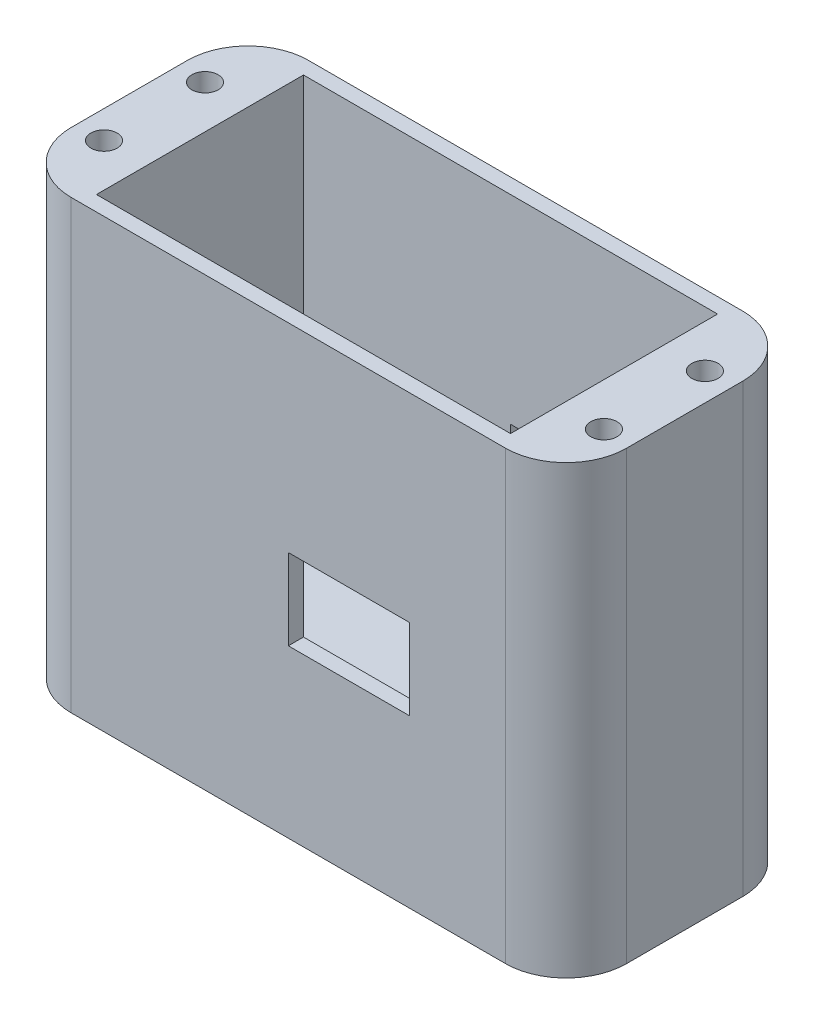
SolidWorks part; units mm, degrees
ref_plane "Front Plane" through (0, 0, 0) normal (0, 0, 1) x (1, 0, 0)
ref_plane "Top Plane" through (0, 0, 0) normal (0, 1, 0) x (1, 0, 0)
ref_plane "Right Plane" through (0, 0, 0) normal (1, 0, 0) x (0, 0, -1)
sketch "Sketch1" plane through (0, 0, 0) normal (0, 1, 0) x (1, 0, 0)
  line L1 (-27.5, 11) -> (27.5, 11)
  line L2 (-27.5, 11) -> (-27.5, -11)
  line L3 (-27.5, -11) -> (27.5, -11)
  line L4 (27.5, 11) -> (27.5, -11)
  line L5 (-27.5, 11) -> (27.5, -11) construction
  line L6 (-27.5, -11) -> (27.5, 11) construction
  point P4 (0, 0)
  dimension "D1" = 22
  dimension "D2" = 55
extrude "Boss-Extrude1" add sketch "Sketch1" along normal blind 2
sketch "Sketch2" plane through (0, 2, 0) normal (0, 1, 0) x (1, 0, 0)
  line L0 (-27.5, -11) -> (-27.5, 11)
  line L1 (-27.5, 11) -> (27.5, 11)
  line L2 (27.5, 11) -> (27.5, -11)
  line L3 (27.5, -11) -> (20.5, -11)
  line L4 (-27.5, -11) -> (27.5, -11) construction
  line L5 (20.5, -11) -> (20.5, 9.5)
  line L6 (20.5, 9.5) -> (-20.5, 9.5)
  line L7 (-20.5, 9.5) -> (-20.5, -11)
  line L8 (-20.5, -11) -> (-27.5, -11)
  dimension "D1" = 7
  dimension "D2" = 7
  dimension "D3" = 1.5
extrude "Boss-Extrude2" add sketch "Sketch2" along normal blind 32.2
sketch "Sketch5" plane through (0, 34.2, 0) normal (0, 1, 0) x (1, 0, 0)
  line L0 (0, 0) -> (0, -6) construction
  line L1 (-24.75, 4) -> (24.75, 4) construction
  line L2 (-24.75, 4) -> (-24.75, -6) construction
  line L3 (-24.75, -6) -> (24.75, -6) construction
  line L4 (24.75, 4) -> (24.75, -6) construction
  line L5 (-24.75, 4) -> (24.75, -6) construction
  line L6 (-24.75, -6) -> (24.75, 4) construction
  line L8 (-27.5, -11) -> (-20.5, -11) construction
  circle A0 centre (-24.75, -6) radius 1.3
  circle A1 centre (-24.75, 4) radius 1.3
  circle A2 centre (24.75, 4) radius 1.3
  circle A3 centre (24.75, -6) radius 1.3
  point P11 (0, -1)
  dimension "D1" = 2.6
  dimension "D2" = 10
  dimension "D3" = 49.5
  dimension "D4" = 5
extrude "Cut-Extrude2" cut sketch "Sketch5" against normal blind 8
sketch "Sketch8" plane through (0, 0, 0) normal (0, -1, 0) x (1, 0, 0)
  line L0 (20.5, 0) -> (11, 0) construction
  line L4 (20.5, -9.5) -> (20.5, 11) construction
  line L7 (11, 0) -> (11, -11)
  line L8 (27.5, -11) -> (-27.5, -11) construction
  circle A0 centre (11, 0) radius 3.2
  circle A1 centre (11, 0) radius 6.6
  dimension "D1" = 9.5
sketch "Sketch10" plane through (0, 0, -9.5) normal (0, 0, 1) x (1, 0, 0)
  line L0 (20.5, 15.13) -> (12, 15.13) construction
  line L1 (20.5, 34.2) -> (20.5, 2) construction
  line L2 (12, 14.5) -> (12, 6.5)
  line L4 (-20.5, 2) -> (20.5, 2) construction
  line L5 (12, 14.5) -> (0, 14.5)
  line L6 (0, 14.5) -> (0, 6.5)
  line L7 (0, 6.5) -> (12, 6.5)
  line L8 (12, 6.5) -> (12, 2) construction
  line L9 (12, 14.5) -> (12, 34.2) construction
  line L10 (-20.5, 34.2) -> (20.5, 34.2) construction
  dimension "D1" = 4.5
  dimension "D2" = 8.5
  dimension "D3" = 12
extrude "Boss-Extrude3" add sketch "Sketch1<2>" against normal blind 10
sketch "Sketch1<2>" plane through (0, 0, 0) normal (0, 1, 0) x (1, 0, 0) same geometry as "Sketch1"
sketch "Sketch11" plane through (0, -10, 0) normal (0, -1, 0) x (1, 0, 0)
  line L0 (0, 11) -> (0, -11) construction
  line L1 (-27.5, 11) -> (27.5, 11) construction
  line L2 (27.5, -11) -> (-27.5, -11) construction
  line L3 (4.9427, 4.9427) -> (-4.9427, -4.9427) construction
  line L4 (4.9427, 4.9427) -> (-4.9427, 4.9427) construction
  line L5 (4.9427, 4.9427) -> (4.9427, -4.9427) construction
  line L6 (4.9427, -4.9427) -> (-4.9427, -4.9427) construction
  line L7 (-4.9427, 4.9427) -> (-4.9427, -4.9427) construction
  line L8 (14.8281, 4.9427) -> (4.9427, 4.9427) construction
  line L9 (14.8281, 4.9427) -> (14.8281, -4.9427) construction
  line L10 (14.8281, -4.9427) -> (4.9427, -4.9427) construction
  line L11 (4.9427, 4.9427) -> (4.9427, -4.9427) construction
  line L12 (-4.9427, 4.9427) -> (-14.8281, 4.9427) construction
  line L13 (-4.9427, 4.9427) -> (-4.9427, -4.9427) construction
  line L14 (-4.9427, -4.9427) -> (-14.8281, -4.9427) construction
  line L15 (-14.8281, 4.9427) -> (-14.8281, -4.9427) construction
  line L16 (4.9427, -4.9427) -> (-4.9427, 4.9427) construction
  line L17 (0, 0) -> (0, -5.1798) construction
  circle A0 centre (14.8281, -4.9427) radius 1.5
  circle A1 centre (14.8281, 4.9427) radius 1.5
  circle A2 centre (4.9427, -4.9427) radius 1.5
  circle A3 centre (4.9427, 4.9427) radius 1.5
  circle A4 centre (-4.9427, -4.9427) radius 1.5
  circle A5 centre (-4.9427, 4.9427) radius 1.5
  circle A6 centre (-14.8281, -4.9427) radius 1.5
  circle A7 centre (-14.8281, 4.9427) radius 1.5
  point P14 (0, 4.9427)
  point P19 (0, 0)
extrude "Cut-Extrude8" cut sketch "Sketch11" against normal blind 10
extrude "Cut-Extrude9" cut sketch "Sketch8" against normal through all and the other way blind 5 contours L0 A0 L7 | A0 L0 L7 region at (12.3581, 0, -1.3581) region at (10.5473, 0, 0.4527)
extrude "Cut-Extrude10" cut sketch "Sketch8<4>" against normal blind 10 contours A1
sketch "Sketch8<4>" plane through (0, 0, 0) normal (0, -1, 0) x (1, 0, 0) same geometry as "Sketch8"
sketch "Sketch12" plane through (0, 0, 11) normal (0, 0, 1) x (1, 0, 0)
  line L1 (27.5, 34.2) -> (-27.5, 34.2)
  line L2 (27.5, 34.2) -> (27.5, -10)
  line L3 (27.5, -10) -> (-27.5, -10)
  line L4 (-27.5, 34.2) -> (-27.5, -10)
extrude "Boss-Extrude4" add sketch "Sketch12" along normal blind 1.5
fillet "Fillet1" radius 6 4 edges at (-27.5, 12.1, 12.5) (-27.5, 12.1, -11) (27.5, 12.1, 12.5) (27.5, 12.1, -11)
extrude "Cut-Extrude7" cut sketch "Sketch10" against normal through all and the other way through all
